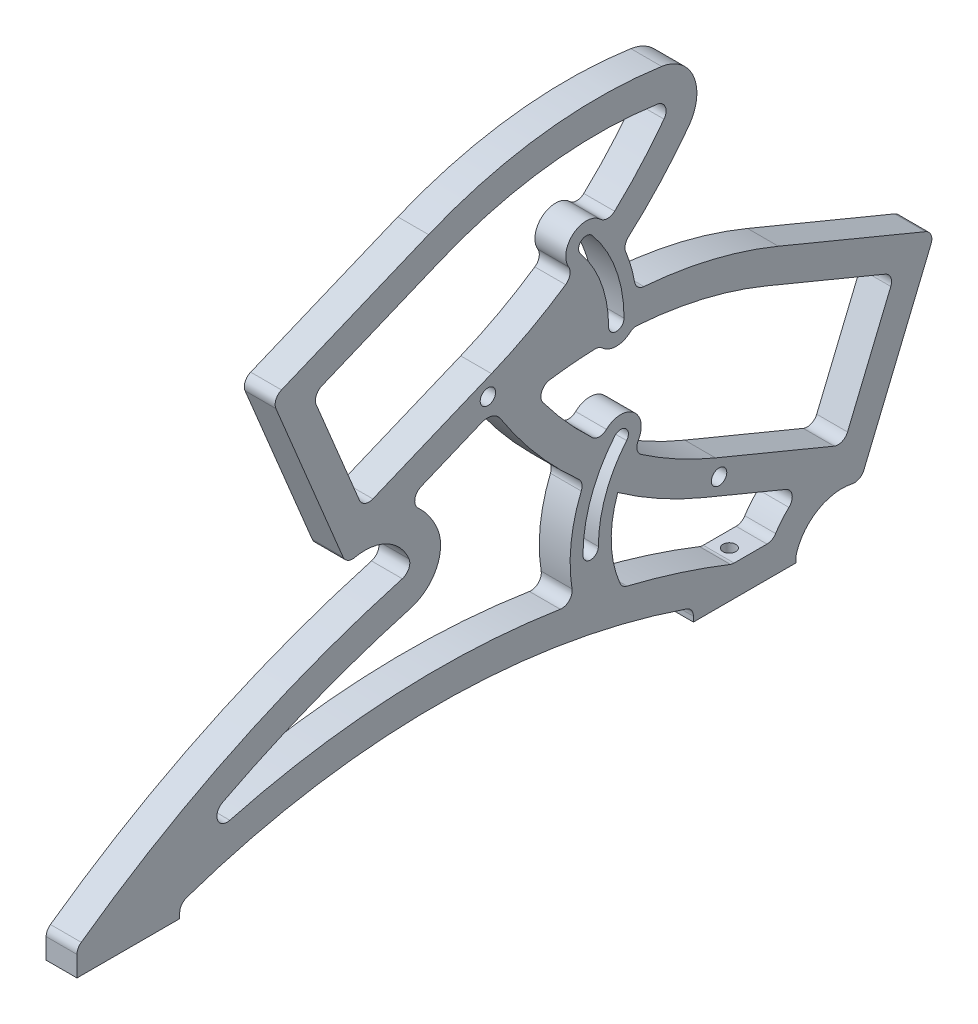
SolidWorks part; units mm, degrees
material "1060 Alloy"
ref_plane "Front Plane" through (0, 0, 0) normal (0, 0, 1) x (1, 0, 0)
ref_plane "Top Plane" through (0, 0, 0) normal (0, 1, 0) x (1, 0, 0)
ref_plane "Right Plane" through (0, 0, 0) normal (1, 0, 0) x (0, 0, -1)
sketch "Sketch1" plane through (0, 0, 0) normal (1, 0, 0) x (0, 0, -1)
  line L0 (0, 0) -> (0, 5)
  line L1 (38.8897, 78.8553) -> (54.5797, 40.9762) construction
  line L2 (38.8897, 78.8553) -> (112.8001, 109.47) construction
  line L3 (54.5797, 40.9762) -> (128.4901, 71.5909) construction
  line L4 (41.8855, 76.849) -> (54.1314, 47.2849) construction
  line L5 (112.8001, 109.47) -> (128.4901, 71.5909) construction
  line L6 (20, 1) -> (20, 0)
  line L7 (0, 0) -> (20, 0)
  line L8 (54.1314, 47.2849) -> (81.8478, 58.7654) construction
  line L9 (69.6019, 88.3295) -> (41.8855, 76.849) construction
  line L10 (80, 58) -> (105, 58) construction
  line L11 (99.1511, 74.0697) -> (80, 58) construction
  line L12 (100, 22) -> (125, 22) construction
  line L13 (125, 22) -> (105.8489, 38.0697) construction
  line L14 (166.1103, 42.8553) -> (150.4203, 4.9762) construction
  line L15 (166.1103, 42.8553) -> (92.1999, 73.47) construction
  line L16 (150.4203, 4.9762) -> (76.5099, 35.5909) construction
  line L17 (92.1999, 73.47) -> (76.5099, 35.5909) construction
  line L18 (150.8686, 11.2849) -> (163.1145, 40.849) construction
  line L19 (163.1145, 40.849) -> (135.3981, 52.3295) construction
  line L20 (123.1522, 22.7654) -> (150.8686, 11.2849) construction
  line L21 (156.9916, 26.0669) -> (84.929, 55.9162) construction
  line L22 (48.0084, 62.0669) -> (120.071, 91.9162) construction
  line L23 (152.4922, 7.3652) -> (167.0342, 42.4726)
  line L24 (167.0342, 42.4726) -> (136.5462, 55.1012)
  line L25 (68.4538, 91.1012) -> (37.9658, 78.4726)
  line L26 (37.9658, 78.4726) -> (52.5078, 43.3652)
  line L27 (63.7245, 48.0113) -> (78.7592, 54.2389)
  line L28 (140, 0) -> (140, 1)
  line L29 (152.4922, 7.3652) -> (143.6238, 11.0386) construction
  line L30 (80.6997, 61.537) -> (55.755, 51.2046)
  line L31 (55.755, 51.2046) -> (45.8052, 75.2254)
  line L32 (45.8052, 75.2254) -> (70.7499, 85.5579)
  line L33 (124.3003, 25.537) -> (149.245, 15.2046)
  line L34 (149.245, 15.2046) -> (159.1948, 39.2254)
  line L35 (159.1948, 39.2254) -> (134.2501, 49.5579)
  line L36 (56.0604, 34.7884) -> (62.7895, 37.5756) construction
  line L37 (52.5078, 43.3652) -> (58.8317, 45.9846) construction
  line L38 (122.0042, 19.9937) -> (141.2755, 12.0113)
  line L39 (135.4645, 6) -> (127.5413, 6)
  line L43 (140, 0) -> (120, 0)
  line L56 (120, 1) -> (120, 0)
  line L63 (174.6584, 98) -> (-14.1241, 98) construction
  circle A0 centre (80, 58) radius 1.5
  circle A1 centre (125, 22) radius 1.5
  arc A2 (99.1511, 74.0697) -> (105, 58) centre (80, 58) cw construction
  arc A3 (106.5, 58) -> (100.3002, 75.0339) centre (80, 58) ccw
  arc A4 (103.5, 58) -> (98.002, 73.1055) centre (80, 58) ccw
  arc A5 (103.5, 58) -> (106.5, 58) centre (105, 58) ccw
  arc A6 (100.3002, 75.0339) -> (98.002, 73.1055) centre (99.1511, 74.0697) ccw
  arc A7 (105.8489, 38.0697) -> (100, 22) centre (125, 22) ccw construction
  arc A8 (104.6998, 39.0339) -> (98.5, 22) centre (125, 22) ccw
  arc A9 (106.998, 37.1055) -> (101.5, 22) centre (125, 22) ccw
  arc A10 (106.998, 37.1055) -> (104.6998, 39.0339) centre (105.8489, 38.0697) ccw
  arc A11 (98.5, 22) -> (101.5, 22) centre (100, 22) ccw
  arc A12 (81.8478, 58.7654) -> (116.6864, 85.8633) centre (49.9981, 135.6573) ccw construction
  arc A13 (116.6864, 85.8633) -> (113.3977, 93.803) centre (112.68, 88.8548) ccw construction
  arc A14 (113.3977, 93.803) -> (69.6019, 88.3295) centre (101.4516, 11.4375) ccw construction
  arc A15 (135.3981, 52.3295) -> (91.6023, 57.803) centre (103.5484, -24.5625) ccw construction
  arc A16 (91.6023, 57.803) -> (88.3136, 49.8633) centre (92.32, 52.8548) ccw construction
  arc A17 (88.3136, 49.8633) -> (123.1522, 22.7654) centre (155.0019, 99.6573) ccw construction
  arc A18 (106.2569, 70.3115) -> (108.7873, 61.5055) centre (80, 58) cw
  arc A19 (106.2569, 70.3115) -> (119.0902, 84.0685) centre (49.9981, 135.6573) ccw
  arc A20 (119.0902, 84.0685) -> (113.8283, 96.7719) centre (112.68, 88.8548) ccw
  arc A21 (113.8283, 96.7719) -> (68.4538, 91.1012) centre (101.4516, 11.4375) ccw
  arc A22 (78.7592, 54.2389) -> (82.432, 53.0875) centre (79.9072, 51.4672) cw
  arc A23 (82.432, 53.0875) -> (98.7431, 34.3115) centre (155.0019, 99.6573) ccw
  arc A24 (152.4922, 7.3652) -> (140.0944, 1.6073) centre (148.9396, -1.2116) ccw
  arc A25 (140.0944, 1.6073) -> (140, 1) centre (142, 1) ccw
  arc A26 (20, 1) -> (21.3514, 2.8919) centre (22, 1) cw
  arc A27 (52.5078, 43.3652) -> (64.6372, 38.341) centre (56.0604, 34.7884) cw
  arc A28 (70.7499, 85.5579) -> (112.9671, 90.8341) centre (101.4516, 11.4375) cw
  arc A29 (112.9671, 90.8341) -> (114.2826, 87.6582) centre (112.68, 88.8548) cw
  arc A30 (114.2826, 87.6582) -> (103.1061, 75.5245) centre (49.9981, 135.6573) cw
  arc A31 (103.1061, 75.5245) -> (102.2153, 76.6408) centre (80, 58) ccw
  arc A32 (102.2153, 76.6408) -> (96.0869, 71.4985) centre (99.1511, 74.0697) ccw
  arc A33 (96.0869, 71.4985) -> (96.8505, 70.5324) centre (80, 58) cw
  arc A34 (96.8505, 70.5324) -> (80.6997, 61.537) centre (49.9981, 135.6573) cw
  arc A35 (134.2501, 49.5579) -> (108.1485, 55.5328) centre (103.5484, -24.5625) ccw
  arc A36 (101.7667, 55.645) -> (92.0329, 54.8341) centre (103.5484, -24.5625) ccw
  arc A37 (92.0329, 54.8341) -> (90.7174, 51.6582) centre (92.32, 52.8548) ccw
  arc A38 (90.7174, 51.6582) -> (101.8939, 39.5245) centre (155.0019, 99.6573) ccw
  arc A39 (101.7667, 55.645) -> (108.1485, 55.5328) centre (105, 58) ccw
  arc A40 (101.8939, 39.5245) -> (102.7847, 40.6408) centre (125, 22) cw
  arc A41 (102.7847, 40.6408) -> (108.9131, 35.4985) centre (105.8489, 38.0697) cw
  arc A42 (108.1495, 34.5324) -> (124.3003, 25.537) centre (155.0019, 99.6573) ccw
  arc A43 (108.9131, 35.4985) -> (108.1495, 34.5324) centre (125, 22) ccw
  arc A44 (120, 1) -> (118.6486, 2.8919) centre (118, 1) ccw
  arc A45 (118.6486, 2.8919) -> (21.3514, 2.8919) centre (70, -139) ccw
  arc A46 (64.6372, 38.341) -> (63.3305, 35.6502) centre (62.7895, 37.5756) cw
  arc A47 (63.3305, 35.6502) -> (0, 5) centre (117.4338, -156.8929) ccw
  arc A48 (98.7431, 34.3115) -> (96.9455, 14.6553) centre (125, 22) ccw
  arc A49 (96.9455, 14.6553) -> (11.4386, 5.591) centre (70, -139) ccw
  arc A50 (11.4386, 5.591) -> (64.9536, 29.8739) centre (117.4338, -156.8929) cw
  arc A51 (63.7245, 48.0113) -> (70.1805, 40.6371) centre (56.0604, 34.7884) cw
  arc A52 (64.9536, 29.8739) -> (70.1805, 40.6371) centre (62.7895, 37.5756) ccw
  arc A53 (105.2771, 29.2117) -> (106.1445, 12.755) centre (125, 22) ccw
  arc A54 (106.1445, 12.755) -> (127.5413, 6) centre (70, -139) cw
  arc A55 (141.2755, 12.0113) -> (135.4645, 6) centre (148.9396, -1.2116) ccw
  arc A56 (136.5462, 55.1012) -> (108.7873, 61.5055) centre (103.5484, -24.5625) ccw
  arc A57 (122.0042, 19.9937) -> (105.2771, 29.2117) centre (155.0019, 99.6573) cw
  point P17 (103.4923, 66.5505)
  point P22 (101.5077, 30.5505)
  dimension "D1" = 3
  dimension "D3" = 1.5
  dimension "D8" = 5
  dimension "D11" = 22
  dimension "D12" = 80
  dimension "D14" = 22.5
  dimension "D16" = 2
  dimension "D17" = 6
  dimension "D21" = 30
  dimension "D22" = 35
  dimension "D23" = 80
  dimension "D24" = 3
  dimension "D18" = 6
  dimension "D29" = 58
  dimension "D25" = 5
  dimension "D28" = 2
  dimension "D36" = 3
  dimension "D37" = 3
  dimension "D38" = 3
  dimension "D39" = 8
  dimension "D40" = 3
  dimension "D45" = 3
  dimension "D46" = 3
  dimension "D47" = 4
  dimension "D48" = 4
  dimension "D49" = 3
  dimension "D52" = 3
  dimension "D53" = 4
  dimension "D54" = 4
  dimension "D55" = 4
  dimension "D56" = 2
  dimension "D57" = 150
  dimension "D58" = 2
  dimension "D59" = 200
  dimension "D60" = 6
  dimension "D61" = 6
  dimension "D62" = 4
  dimension "D63" = 6
  dimension "D64" = 8
  dimension "D67" = 4
  dimension "D68" = 6
  dimension "D69" = 6
  dimension "D2" = 25
  dimension "D4" = 25
  dimension "D5" = 40
  dimension "D6" = 40
  dimension "D7" = 125
  dimension "D9" = 20
  dimension "D10" = 100
  dimension "D13" = 1
  dimension "D15" = 22.5
  dimension "D19" = 30
  dimension "D20" = 30
  dimension "D26" = 3
  dimension "D27" = 2
  dimension "D30" = 3
  dimension "D31" = 3
  dimension "D32" = 98
  dimension "D33" = 3
  dimension "D34" = 3
  dimension "D35" = 3
  dimension "D41" = 3
  dimension "D42" = 3
  dimension "D43" = 3
  dimension "D44" = 3
  dimension "D50" = 3
  dimension "D51" = 3
  dimension "D65" = 6
  dimension "D66" = 3
extrude "Boss-Extrude1" add sketch "Sketch1" along normal blind 6
fillet "Fillet1" radius 2 25 edges at (3, 14.6553, -96.9455) (3, 34.3115, -98.7431) (3, 12.755, -106.1445) (3, 12.0113, -141.2755) (3, 6, -135.4645) (3, 6, -127.5413) (3, 39.5245, -101.8939) (3, 34.5324, -108.1495) (3, 15.2046, -149.245) (3, 39.2254, -159.1948) (3, 42.4726, -167.0342) (3, 7.3652, -152.4922) (3, 75.5245, -103.1061) (3, 70.5324, -96.8505) (3, 51.2046, -55.755) (3, 78.4726, -37.9658) (3, 75.2254, -45.8052) (3, 43.3652, -52.5078) (3, 48.0113, -63.7245) (3, 5.591, -11.4386) (3, 5, 0) (3, 55.5328, -108.1485) (3, 55.645, -101.7667) (3, 61.5055, -108.7873) (3, 70.3115, -106.2569)
hole_wizard "Tap Drill for M3 Tap1" positions "Sketch3" profile "Sketch2" hole size "M3" standard "ISO"
sketch "Sketch3" plane through (0, 0, 0) normal (0, -1, 0) x (-1, 0, 0)
  line L0 (-6, 20) -> (0, 20) construction
  line L1 (0, 0) -> (0, 20) construction
  line L2 (-6, 120) -> (0, 120) construction
  point P0 (-3, 10)
  point P2 (-3, 130)
  dimension "D1" = 10
  dimension "D2" = 3
  dimension "D3" = 10
sketch "Sketch2" plane through (3, 0, -10) normal (1, 0, 0) x (0, 0, -1)
  line L0 (0, 0) -> (0, 10.7511)
  line L1 (0, 10.7511) -> (1.25, 10)
  line L2 (1.25, 10) -> (1.25, 0)
  line L5 (1.25, 0) -> (0, 0)
  line L10 (0, 10.7511) -> (-1.25, 10) construction
  line L11 (0, -6.35) -> (0, 107.95) construction
  dimension "Hole Dia." = 2.5
  dimension "Hole Depth" = 10
  dimension "Drill Angle" = 118
equation "\"ˇ35\"=76.24"
